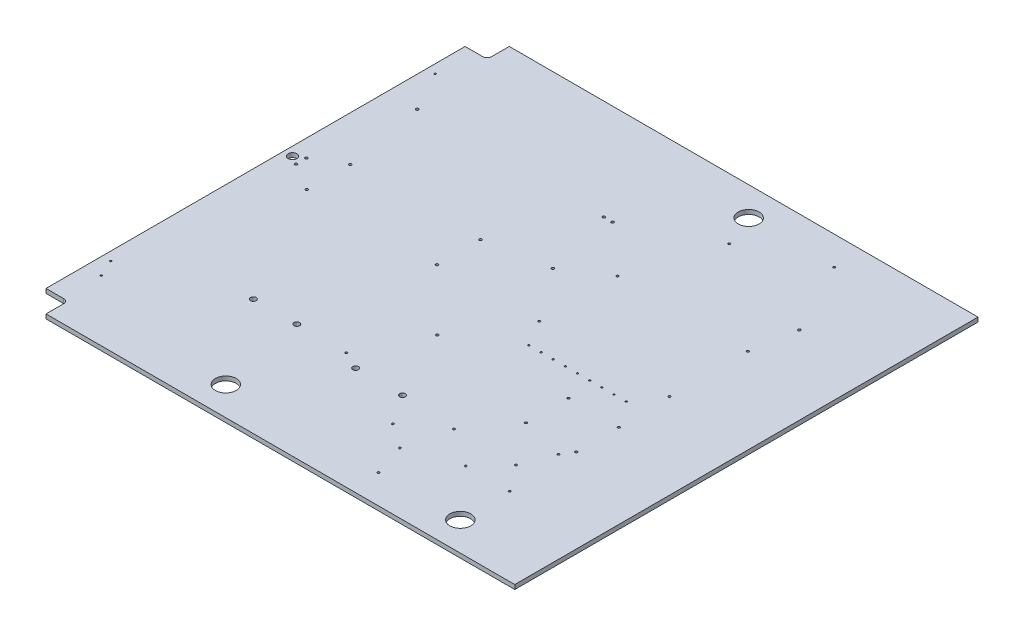
SolidWorks part; units mm, degrees
ref_plane "Front Plane" through (0, 0, 0) normal (0, 0, 1) x (1, 0, 0)
ref_plane "Top Plane" through (0, 0, 0) normal (0, 1, 0) x (1, 0, 0)
ref_plane "Right Plane" through (0, 0, 0) normal (1, 0, 0) x (0, 0, -1)
sketch "Sketch1" plane through (0, 0, 0) normal (1, 0, 0) x (0, 0, -1)
  line L0 (0, 0) -> (-533.4, 0)
  line L1 (-533.4, 0) -> (-533.4, 5)
  line L2 (-533.4, 5) -> (0, 5)
  line L6 (0, 5) -> (0, 0)
  dimension "D1" = 533.4
extrude "Boss-Extrude1" add sketch "Sketch1" along normal blind 565.15
sketch "BotthomHoles-Sketch2" plane through (0, 5, 0) normal (0, 1, 0) x (1, 0, 0)
  line L1 (565.15, 0) -> (565.15, -533.4) construction
  line L2 (565.15, -533.4) -> (0, -533.4) construction
  line L3 (565.15, 0) -> (0, 0) construction
  line L4 (0, 0) -> (0, -533.4) construction
  circle A0 centre (334.275, -33.175) radius 12
  circle A25 centre (199.275, -500.225) radius 12
  circle A26 centre (469.275, -500.225) radius 12
  dimension "D10" = 24
  dimension "D2" = 95.875
  dimension "D3" = 270
  dimension "D4" = 135
  dimension "D5" = 33.175
  dimension "D6" = 33.175
  dimension "D8" = 500.225
  dimension "D7" = 199.275
  dimension "D9" = 334.275
  dimension "D11" = 469.275
extrude "BottomStepperHoles-Cut-Extrude1" cut sketch "BotthomHoles-Sketch2" against normal through all
sketch "BottomPSUHolesSketch2" plane through (0, 5, 0) normal (0, 1, 0) x (1, 0, 0)
  line L0 (0, 0) -> (0, -533.4) construction
  line L1 (565.15, -533.4) -> (0, -533.4) construction
  line L2 (565.15, 0) -> (0, 0) construction
  circle A0 centre (201.5, -209.2) radius 1.5
  circle A1 centre (201.5, -259.2) radius 1.5
  circle A2 centre (51.5, -209.2) radius 1.5
  circle A3 centre (51.5, -259.2) radius 1.5
  circle A6 centre (180, -399.2) radius 3.25
  circle A7 centre (130, -399.2) radius 3.25
  circle A8 centre (257.75, -409.2) radius 3.25
  circle A9 centre (311.75, -409.2) radius 3.25
  dimension "D4" = 6.5
  dimension "D3" = 51.5
  dimension "D1" = 150
  dimension "D2" = 50
  dimension "D7" = 209.2
  dimension "D5" = 50
  dimension "D8" = 140
  dimension "D10" = 134.2
  dimension "D11" = 274.2
  dimension "D12" = 324.2
  dimension "D13" = 201.5
  dimension "D14" = 54
  dimension "D15" = 77.75
  dimension "D16" = 10
  dimension "D9" = 78.5
  dimension "D17" = 130
  dimension "D18" = 124.2
  dimension "D19" = 257.75
  dimension "D20" = 311.75
extrude "BottomPSUHolesCut-Extrude1" cut sketch "BottomPSUHolesSketch2" against normal through all
sketch "OctopusHolesSketch2" plane through (0, 5, 0) normal (0, 1, 0) x (1, 0, 0)
  line L0 (0, 0) -> (0, -533.4) construction
  line L1 (565.15, -533.4) -> (0, -533.4) construction
  circle A0 centre (316.75, -256.7) radius 1.35
  circle A1 centre (466.75, -256.7) radius 1.35
  circle A2 centre (316.75, -166.7) radius 1.35
  circle A3 centre (466.75, -166.7) radius 1.35
  dimension "D1" = 150
  dimension "D3" = 2.7
  dimension "D2" = 90
  dimension "D4" = 115.25
  dimension "D5" = 42.5
  dimension "D6" = 316.75
  dimension "D7" = 466.75
  dimension "D8" = 276.7
  dimension "D9" = 366.7
extrude "OctopusMountHolesCut-Extrude1" cut sketch "OctopusHolesSketch2" against normal through all
sketch "PowrCableGuideMountHolesSketch2" plane through (0, 5, 0) normal (0, 1, 0) x (1, 0, 0)
  line L0 (0, 0) -> (0, -533.4) construction
  line L1 (565.15, -533.4) -> (0, -533.4) construction
  circle A0 centre (271.75, -329.2) radius 1.5
  circle A1 centre (271.75, -196.2) radius 1.5
  dimension "D2" = 3
  dimension "D1" = 133
  dimension "D3" = 45
  dimension "D5" = 271.75
  dimension "D6" = 337.2
  dimension "D7" = 204.2
  dimension "D4" = 29.5
extrude "PowerCableGuideMountHolesCut-Extrude1" cut sketch "PowrCableGuideMountHolesSketch2" against normal through all
sketch "RPIHolesSketch2" plane through (0, 5, 0) normal (0, 1, 0) x (1, 0, 0)
  line L0 (0, 0) -> (0, -533.4) construction
  line L1 (565.15, -533.4) -> (0, -533.4) construction
  circle A4 centre (468.25, -316.7) radius 1.35
  circle A5 centre (468.25, -365.7) radius 1.35
  circle A6 centre (410.25, -316.7) radius 1.35
  circle A7 centre (410.25, -365.7) radius 1.35
  point P4 (282.575, -533.4)
  dimension "D7" = 2.7
  dimension "D1" = 58
  dimension "D2" = 49
  dimension "D3" = 60
  dimension "D4" = 1.5
  dimension "D5" = 410.25
  dimension "D6" = 468.25
  dimension "D8" = 167.7
  dimension "D9" = 216.7
extrude "RPIMountHolesCut-Extrude1" cut sketch "RPIHolesSketch2" against normal through all
sketch "CableHolesSketch2" plane through (0, 5, 0) normal (0, 1, 0) x (1, 0, 0)
  line L3 (565.15, -533.4) -> (0, -533.4) construction
  line L9 (0, 0) -> (0, -533.4) construction
  line L12 (565.15, 0) -> (0, 0) construction
  circle A11 centre (260, -115.65) radius 1.5
  circle A12 centre (10, -234.2) radius 5
  circle A13 centre (19, -463.4) radius 1
  circle A14 centre (10, -70) radius 1
  circle A16 centre (10, -443.4) radius 1
  circle A17 centre (475, -115.65) radius 1.5
  circle A18 centre (250, -115.65) radius 1.5
  circle A19 centre (35, -115.65) radius 1.5
  circle A20 centre (20, -240.2) radius 1.5
  circle A21 centre (20, -228.2) radius 1.5
  dimension "D17" = 3
  dimension "D10" = 10
  dimension "D26" = 3
  dimension "D3" = 70
  dimension "D8" = 10
  dimension "D1" = 70
  dimension "D9" = 20
  dimension "D12" = 90
  dimension "D13" = 299.2
  dimension "D14" = 463.4
  dimension "D15" = 260
  dimension "D5" = 215
  dimension "D16" = 8.25
  dimension "D18" = 475
  dimension "D19" = 215
  dimension "D20" = 10
  dimension "D22" = 35
  dimension "D23" = 250
  dimension "D6" = 25
  dimension "D11" = 10
  dimension "D21" = 6
  dimension "D24" = 6
  dimension "D25" = 20
  dimension "D4" = 10
  dimension "D27" = 19
extrude "CableHolesCut-Extrude1" cut sketch "CableHolesSketch2" against normal through all
sketch "Sketch2" plane through (0, 5, 0) normal (0, 1, 0) x (1, 0, 0)
  line L0 (565.15, -533.4) -> (0, -533.4) construction
  line L1 (0, 0) -> (0, -533.4) construction
  circle A0 centre (334.75, -286.7) radius 1
  circle A1 centre (348.75, -286.7) radius 1
  circle A2 centre (362.75, -286.7) radius 1
  circle A3 centre (376.75, -286.7) radius 1
  circle A4 centre (390.75, -286.7) radius 1
  circle A5 centre (404.75, -286.7) radius 1
  circle A6 centre (418.75, -286.7) radius 1
  circle A7 centre (432.75, -286.7) radius 1
  circle A8 centre (446.75, -286.7) radius 1
  dimension "D10" = 14
  dimension "D11" = 2
  dimension "D1" = 18
  dimension "D2" = 14
  dimension "D3" = 14
  dimension "D4" = 14
  dimension "D5" = 14
  dimension "D6" = 14
  dimension "D7" = 14
  dimension "D8" = 14
  dimension "D9" = 30
  dimension "D12" = 246.7
  dimension "D13" = 334.75
extrude "OctopusRouting holesCut-Extrude1" cut sketch "Sketch2" against normal through all
sketch "Sketch3" plane through (0, 5, 0) normal (0, 1, 0) x (1, 0, 0)
  line L0 (565.15, -533.4) -> (0, -533.4) construction
  line L1 (0, 0) -> (0, -533.4) construction
  line L2 (565.15, -533.4) -> (0, -533.4) construction
  circle A0 centre (469.275, -443.4) radius 1.25
  circle A1 centre (418.75, -443.4) radius 1.25
  circle A2 centre (446.75, -413.4) radius 1.25
  circle A3 centre (375, -413.4) radius 1.25
  circle A4 centre (375, -500.225) radius 1.25
  circle A5 centre (362.75, -463.4) radius 1.25
  circle A6 centre (334.75, -443.4) radius 1.25
  circle A7 centre (432.75, -33.175) radius 1.25
  circle A8 centre (348.75, -70) radius 1.25
  circle A10 centre (237, -399.2) radius 1.25
  circle A11 centre (460.5, -378.4) radius 1.25
  dimension "D3" = 2.5
  dimension "D1" = 90
  dimension "D2" = 469.275
  dimension "D4" = 418.75
  dimension "D5" = 120
  dimension "D6" = 446.75
  dimension "D7" = 375
  dimension "D8" = 33.175
  dimension "D9" = 70
  dimension "D10" = 362.75
  dimension "D11" = 334.75
  dimension "D12" = 500.225
  dimension "D13" = 432.75
  dimension "D14" = 463.4
  dimension "D15" = 348.75
  dimension "D16" = 134.2
  dimension "D18" = 237
  dimension "D19" = 460.5
  dimension "D20" = 155
extrude "CornerClampHoleCuts-Extrude1" cut sketch "Sketch3" against normal through all
sketch "CornerCableKnotchesSketch4" plane through (0, 5, 0) normal (0, 1, 0) x (1, 0, 0)
  line L0 (0, -25.4) -> (20.4, -25.4)
  line L1 (25.4, 0) -> (25.4, -20.4)
  line L2 (565.15, 0) -> (0, 0) construction
  line L3 (0, -25.4) -> (0, 0)
  line L4 (0, 0) -> (0, -533.4) construction
  line L5 (0, 0) -> (25.4, 0)
  line L6 (0, -508) -> (20.4, -508)
  line L7 (25.4, -513) -> (25.4, -533.4)
  line L8 (565.15, -533.4) -> (0, -533.4) construction
  line L9 (0, -508) -> (0, -533.4)
  line L10 (0, -533.4) -> (25.4, -533.4)
  arc A0 (20.4, -25.4) -> (25.4, -20.4) centre (20.4, -20.4) ccw
  arc A1 (25.4, -513) -> (20.4, -508) centre (20.4, -513) ccw
  circle A2 centre (25, -115.65) radius 5 construction
  dimension "D1" = 25.4
extrude "CornerCableKnotchCut-Extrude1" cut sketch "CornerCableKnotchesSketch4" against normal through all
equation "\"RailThickness\"= .125in'Spec"
equation "\"Nema17MountStepperHoleDiameter\"= 24mm'Spec"
equation "\"SideRailLength\"= 21.75in"
equation "\"D10@BotthomHoles-Sketch2\" = \"Nema17MountStepperHoleDiameter\""
equation "\"D1@Boss-Extrude1\"=\"LowerEnclosureLength\""
equation "\"BedLength\"= \"BuildPlateLength\""
equation "\"DistanceBetweenFrontToBackStepperHoles\"= \"BedLength\" - \"BuildPlateStandoffHolesDistanceFromFrontOrBackSide\" * 2'Equals 270"
equation "\"LowerEnclosureThickness\"= 5mm"
equation "\"FrontOrBackRailLength\"= 20.5in"
equation "\"D1@Sketch1\"=\"LowerEncloseWidth\""
equation "\"D2@Sketch1\"=\"LowerEnclosureThickness\""
equation "\"24VPSUMountingHolesShortDistanceBetween\"= 50mm'Yours may differ"
equation "\"24VPSUMountingHolesLongDistanceBetween\"= 150mm'Yours may differ"
equation "\"24VPSUMountingHoleOffsetFromEitherSide\"= 32.5mm'Yours may differ"
equation "\"24VPSUMountingHoleDiameter\"= 3mm'Yours may differ"
equation "\"D6@BottomPSUHolesSketch2\" = \"24VPSUMountingHoleDiameter\""
equation "\"RPi4BoardMountingHoleDiameter\"= 2.7mm'Spec"
equation "\"OctopusV1.1BoardMountingHoleOffsetFromAllEdges\"= 5mm'Spec"
equation "\"OctopusV1.1BoardMountingHoleLengthDistanceBetween\"= 150mm'Spec"
equation "\"OctopusV1.1BoardMountingHoleWidthDistanceBetween\"= 90mm'Spec"
equation "\"D7@RPIHolesSketch2\" = \"RPi4BoardMountingHoleDiameter\""
equation "\"RPi4BoardMountingHoleLengthDistanceBetween\"= 58mm'Spec"
equation "\"OctopusV1.1BoardMountingHoleDiameter\"= 2.7mm'Spec"
equation "\"CWD4890MountingHoleWidthDistance\"= 50mm'Spec"
equation "\"24VPSULength\"= 213mm'Spec"
equation "\"D3@OctopusHolesSketch2\"=\"OctopusV1.1BoardMountingHoleDiameter\""
equation "\"24VPSUMountingHoleOffsetFromFront\"= 32.5mm"
equation "\"DistanceBetween24VPSUAndOctopus\"= \"24VPSUMountingHoleOffsetFromFront\" + \"OctopusV1.1BoardMountingHoleOffsetFromAllEdges\" + 77.75'77.75mm gives 10mm before and after 60mm cable guide"
equation "\"GapBetweenVerticalSupportsAndRails\"= \"RailThickness\" * 2"
equation "\"LowerEncloseWidth\"= \"FrontOrBackRailLength\" + \"GapBetweenVerticalSupportsAndRails\" * 2"
equation "\"Nema17MountStepperHoleFromBack\"= 30mm"
equation "\"D2@BotthomHoles-Sketch2\"=\"DistanceFromFrontSideToFirstLeftStepperHoleMountYSValue\" + \"Nema17StepperMountSlotDistance\"/2 + \"GapBetweenVerticalSupportsAndRails\""
equation "\"D3@BotthomHoles-Sketch2\"=\"DistanceBetweenFrontToBackStepperHoles\""
equation "\"D4@BotthomHoles-Sketch2\"=\"DistanceBetweenFrontToBackStepperHoles\"/2"
equation "\"D5@BotthomHoles-Sketch2\"=\"Nema17MountStepperHoleFromBack\" + \"RailThickness\""
equation "\"D6@BotthomHoles-Sketch2\"=\"Nema17MountStepperHoleFromBack\" + \"RailThickness\""
equation "\"LowerEnclosureLength\"= \"SideRailLength\" + \"GapBetweenVerticalSupportsAndRails\" * 2"
equation "\"DistanceFromFrontSideToFirstLeftStepperHoleMountYSValue\"= 74.025mm"
equation "\"BuildPlateStandoffHolesDistanceFromFrontOrBackSide\"= 41mm"
equation "\"BuildPlateLength\"= 352mm'Spec"
equation "\"D1@BottomPSUHolesSketch2\"=\"24VPSUMountingHolesLongDistanceBetween\""
equation "\"D2@BottomPSUHolesSketch2\"=\"24VPSUMountingHolesShortDistanceBetween\""
equation "\"24VPSUOffsetFromBack\"= ( \"24VPSULength\" - \"24VPSUMountingHolesLongDistanceBetween\" ) / 2 + 20mm"
equation "\"24VPSUOffsetFromRightSide\"= ( \"LowerEncloseWidth\" - \"24VPSUWidth\" ) / 2"
equation "\"24VPSUWidth\"= 115mm'Yours may differ"
equation "\"D3@BottomPSUHolesSketch2\"=\"24VPSUOffsetFromBack\""
equation "\"D1@OctopusHolesSketch2\"=\"OctopusV1.1BoardMountingHoleLengthDistanceBetween\""
equation "\"D2@OctopusHolesSketch2\"=\"OctopusV1.1BoardMountingHoleWidthDistanceBetween\""
equation "\"D4@OctopusHolesSketch2\" = \"DistanceBetween24VPSUAndOctopus\""
equation "\"RPI4BoardMountingHoleWidthDistanceBetween\"= 49mm"
equation "\"D7@BottomPSUHolesSketch2\"=\"24VPSUOffsetFromRightSide\""
equation "\"D1@RPIHolesSketch2\"=\"RPi4BoardMountingHoleLengthDistanceBetween\""
equation "\"D2@RPIHolesSketch2\"=\"RPI4BoardMountingHoleWidthDistanceBetween\""
equation "\"D5@BottomPSUHolesSketch2\"=\"CWD4890MountingHoleWidthDistance\""
equation "\"OctopusV1.1ToPSUNegTerminalOffset\"= \"24VPSUNegTerminalOffsetFromSide\" - \"24VPSUMountingHoleOffsetFromEitherSide\" + \"OctopusV1.1NegTerminalOffsetFromSide\" + \"OctopusV1.1BoardMountingHoleOffsetFromAllEdges\""
equation "\"24VPSUNegTerminalOffsetFromSide\"= 50.5mm"
equation "\"OctopusV1.1NegTerminalOffsetFromSide\"= 19.5mm"
equation "\"D5@OctopusHolesSketch2\" = \"OctopusV1.1ToPSUNegTerminalOffset\""
equation "\"PowerCableGuideMountingHoleDistanceBetweenValue\"=133"
equation "\"D1@PowrCableGuideMountHolesSketch2\" = \"PowerCableGuideMountingHoleDistanceBetweenValue\""
equation "\"D2@PowrCableGuideMountHolesSketch2\" = \"24VPSUMountingHoleDiameter\""
equation "\"RCNUNMountingHoleWidthDistance\"= 54mm"
equation "\"D14@BottomPSUHolesSketch2\"=\"RCNUNMountingHoleWidthDistance\""
equation "\"OctopusToPowerCableGuideOffset\"= 29.5mm'This asligned perfectly"
equation "\"D4@PowrCableGuideMountHolesSketch2\"=\"OctopusToPowerCableGuideOffset\""
equation "\"VSWidth\"= 1.25in'Spec"
equation "\"D1@CornerCableKnotchesSketch4\" = \"VSWidth\" - \"RailThickness\" * 2"
equation "\"Nema17StepperMountSlotDistance\"= 31mm'Spec"
equation "\"D6@CableHolesSketch2\"=\"24VPSUMountingHolesShortDistanceBetween\"/2"
